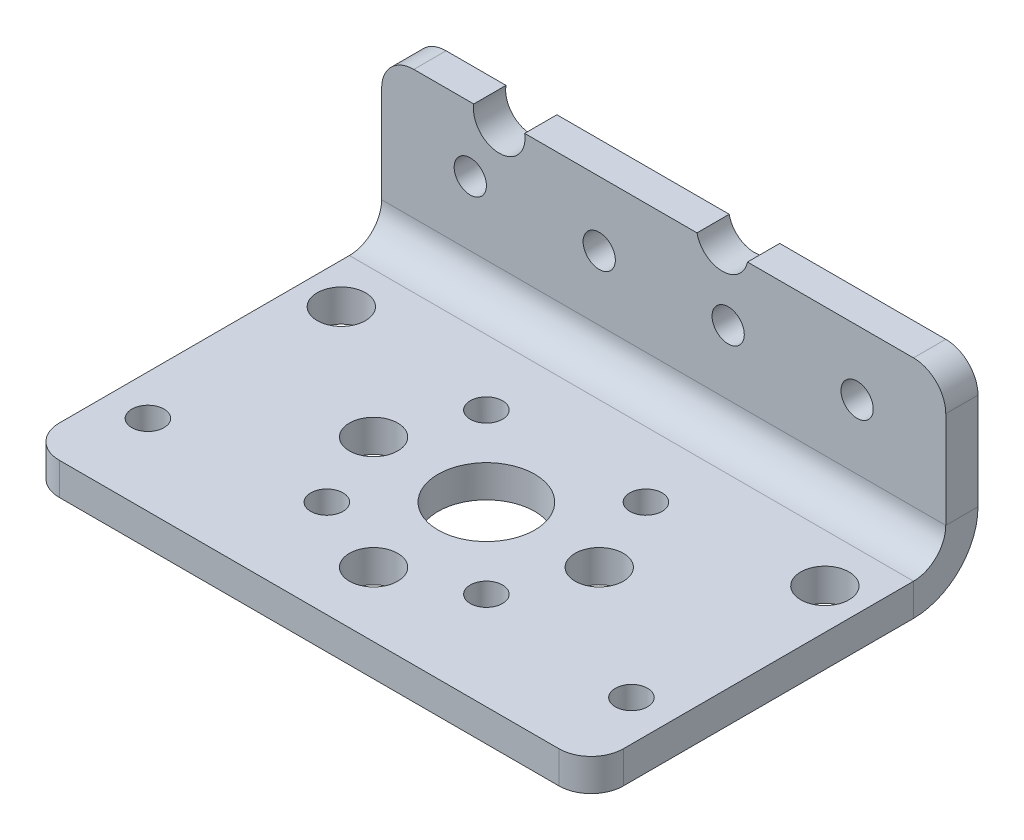
SolidWorks part; units mm, degrees
note: The reader was unsure of these and kept them because the rebuilt part matched: flange length of "Edge-Flange1".
material "Galvanized Steel"
ref_plane "Front Plane" through (0, 0, 0) normal (0, 0, 1) x (1, 0, 0)
ref_plane "Top Plane" through (0, 0, 0) normal (0, 1, 0) x (1, 0, 0)
ref_plane "Right Plane" through (0, 0, 0) normal (1, 0, 0) x (0, 0, -1)
sketch "Sketch1" plane through (0, 0, 0) normal (0, 0, 1) x (1, 0, 0)
  line L1 (17.5, -6) -> (-17.5, -6)
  line L2 (17.5, -6) -> (17.5, 6)
  line L3 (17.5, 6) -> (-17.5, 6)
  line L4 (-17.5, -6) -> (-17.5, 6)
  line L5 (17.5, -6) -> (-17.5, 6) construction
  line L6 (17.5, 6) -> (-17.5, -6) construction
  point P0 (0, 0)
  dimension "D1" = 35
  dimension "D2" = 12
base flange "Base-Flange1" sketch "Sketch1" thickness 2 reverse thickness direction no parameters "D1"=2
edge flange "Edge-Flange1" sketch "Sketch8" flange angle 90 flange length 24 flange position material inside bend radius 2 thickness 2 relief rectangular parameters "D6"=10
sketch "Sketch8" plane through (0, -6, 0) normal (0, -1, 0) x (1, 0, 0)
  line L2 (-17.5, 0) -> (-17.5, 22)
  line L3 (-17.5, 22) -> (17.5, 22)
  line L4 (17.5, 22) -> (17.5, 0)
  line L7 (-17.5, 0) -> (17.5, 0) construction
  line L8 (-17.5, 0) -> (17.5, 0)
bend "EdgeBend1" bend radius 2 bend angle 90 parameters "D5"=1
fillet "Fillet1" radius 2 4 edges at (-17.5, 6, -1) (17.5, 6, -1) (17.5, -5, 22) (-17.5, -5, 22)
sketch "Sketch9" plane through (0, 0, -2) normal (0, 0, -1) x (-1, 0, 0)
  line L0 (0, 6) -> (0, 2) construction
  line L1 (-17.5, 6) -> (17.5, 6) construction
  line L2 (0, 2) -> (4, 2) construction
  line L3 (4, 2) -> (12, 2) construction
  circle A0 centre (4, 2) radius 1
  circle A1 centre (12, 2) radius 1
  circle A2 centre (-12, 2) radius 1
  circle A3 centre (-4, 2) radius 1
  dimension "D2" = 2
  dimension "D5" = 2
  dimension "D1" = 4
  dimension "D3" = 4
  dimension "D4" = 8
extrude "Cut-Extrude1" cut sketch "Sketch9" against normal blind 10 normal cut yes
sketch "Sketch10" plane through (0, -6, 0) normal (0, -1, 0) x (1, 0, 0)
  line L0 (0, 22) -> (0, 11) construction
  line L1 (-17.5, 22) -> (17.5, 22) construction
  line L2 (0, 11) -> (-7, 11) construction
  line L3 (-4.9497, 15.9497) -> (0, 11) construction
  line L4 (-4.9497, 6.0503) -> (0, 11) construction
  circle A0 centre (0, 11) radius 3
  circle A1 centre (-7, 11) radius 1.5
  circle A2 centre (-15, 5) radius 1.5
  circle A3 centre (-15, 17) radius 1
  circle A4 centre (-4.9497, 15.9497) radius 1
  circle A5 centre (-4.9497, 6.0503) radius 1
  circle A6 centre (0, 18) radius 1.5
  circle A7 centre (0, 11) radius 7 construction
  circle A8 centre (15, 17) radius 1
  circle A9 centre (15, 5) radius 1.5
  circle A10 centre (4.9497, 6.0503) radius 1
  circle A11 centre (7, 11) radius 1.5
  circle A12 centre (4.9497, 15.9497) radius 1
  dimension "D1" = 6
  dimension "D3" = 3
  dimension "D9" = 3
  dimension "D10" = 2
  dimension "D11" = 2
  dimension "D12" = 2
  dimension "D13" = 3
  dimension "D16" = 14
  dimension "D2" = 11
  dimension "D4" = 7
  dimension "D5" = 15
  dimension "D6" = 6
  dimension "D7" = 6
  dimension "D8" = 15
  dimension "D14" = 7
  dimension "D15" = 45
  dimension "D17" = 45
extrude "Cut-Extrude2" cut sketch "Sketch10" against normal blind 10 normal cut yes
sketch "Sketch11" plane through (0, 0, 0) normal (0, 0, 1) x (1, 0, 0)
  circle A0 centre (-10.206, 5.7439) radius 1.6
  circle A1 centre (3.6318, 6.3238) radius 1.6
extrude "Cut-Extrude3" cut sketch "Sketch11" against normal blind 10 normal cut yes
sketch "Bend-Lines1" [suppressed] plane through (0, 0, 0) normal (0, 1, 0) x (1, 0, 0)
sketch "Bounding-Box1" [suppressed] plane through (0, 0, 0) normal (0, 1, 0) x (1, 0, 0)
sheet metal parameters "Sheet-Metal1" thickness 2 parameters "D1"=2
flat pattern "Flat-Pattern1" [suppressed]
sketch "Bend-Lines2" plane through (0, 0, 0) normal (0, 1, 0) x (1, 0, 0)
sketch3d "Bounding-Box2" [suppressed]
  line L0 (17.5, -6, 0) -> (-17.5, -6, 0) construction
  line L1 (17.5, 6, 0) -> (-17.5, 6, 0) construction
  line L2 (17.5, -6, 0) -> (17.5, 6, 0) construction
  line L3 (-17.5, -6, 0) -> (-17.5, 6, 0) construction
sheet metal parameters "Sheet-Metal2" thickness 2 parameters "D1"=2
flat pattern "Flat-Pattern1"
sketch "Bend-Lines2" plane through (0, 0, 0) normal (0, 0, 1) x (1, 0, 0)
  line L0 (-17.5, -4.75) -> (17.5, -4.75) construction
  line L1 (-17.5, -4.75) -> (17.5, -4.75) construction
sketch3d "Bounding-Box2" [suppressed]
  line L0 (-17.5, 6, 0) -> (17.5, 6, 0) construction
  line L1 (-17.5, -27.5, 0) -> (17.5, -27.5, 0) construction
  line L2 (-17.5, 6, 0) -> (-17.5, -27.5, 0) construction
  line L3 (17.5, 6, 0) -> (17.5, -27.5, 0) construction
bend of the flat pattern "Flatten-<EdgeBend1>1"
sheet metal parameters "Sheet-Metal3" thickness 2 parameters "D1"=2
flat pattern "Flat-Pattern1"
sketch "Bend-Lines2" plane through (0, 0, 0) normal (0, 0, 1) x (1, 0, 0)
  line L0 (-17.5, -4.75) -> (17.5, -4.75) construction
  line L1 (-17.5, -4.75) -> (17.5, -4.75) construction
sketch3d "Bounding-Box2" [suppressed]
  line L0 (-17.5, 6, 0) -> (17.5, 6, 0) construction
  line L1 (-17.5, -27.5, 0) -> (17.5, -27.5, 0) construction
  line L2 (-17.5, 6, 0) -> (-17.5, -27.5, 0) construction
  line L3 (17.5, 6, 0) -> (17.5, -27.5, 0) construction
bend of the flat pattern "Flatten-<EdgeBend1>1"
sheet metal parameters "Sheet-Metal4" thickness 2 parameters "D1"=2
flat pattern "Flat-Pattern1"
sketch "Bend-Lines2" plane through (0, 0, 0) normal (0, 0, 1) x (1, 0, 0)
  line L0 (-17.5, -4.75) -> (17.5, -4.75) construction
  line L1 (-17.5, -4.75) -> (17.5, -4.75) construction
sketch3d "Bounding-Box2" [suppressed]
  line L0 (-17.5, 6, 0) -> (17.5, 6, 0) construction
  line L1 (-17.5, -27.5, 0) -> (17.5, -27.5, 0) construction
  line L2 (-17.5, 6, 0) -> (-17.5, -27.5, 0) construction
  line L3 (17.5, 6, 0) -> (17.5, -27.5, 0) construction
bend of the flat pattern "Flatten-<EdgeBend1>1"
sheet metal parameters "Sheet-Metal5" thickness 2 parameters "D1"=2
flat pattern "Flat-Pattern1"
sketch "Bend-Lines2" plane through (0, 0, 0) normal (0, 0, 1) x (1, 0, 0)
  line L0 (-17.5, -4.75) -> (17.5, -4.75) construction
  line L1 (-17.5, -4.75) -> (17.5, -4.75) construction
sketch3d "Bounding-Box2" [suppressed]
  line L0 (-17.5, 6, 0) -> (17.5, 6, 0) construction
  line L1 (-17.5, -27.5, 0) -> (17.5, -27.5, 0) construction
  line L2 (-17.5, 6, 0) -> (-17.5, -27.5, 0) construction
  line L3 (17.5, 6, 0) -> (17.5, -27.5, 0) construction
bend of the flat pattern "Flatten-<EdgeBend1>1"
